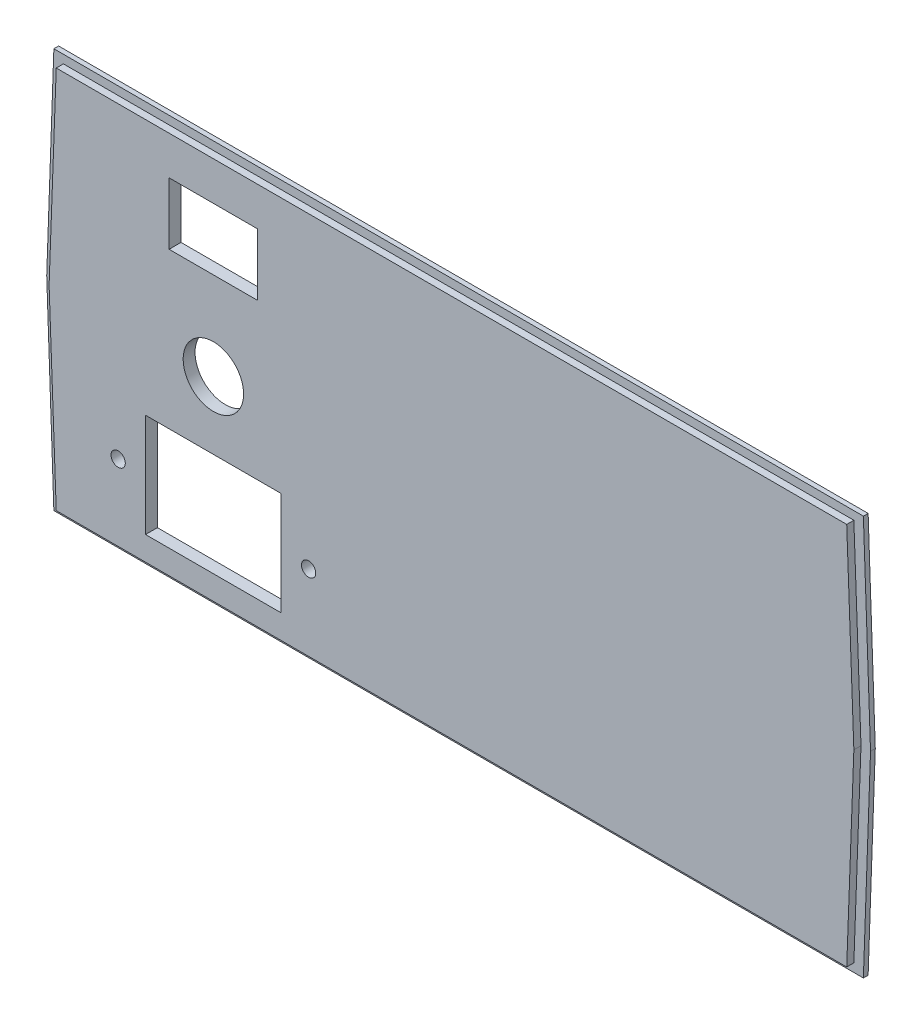
SolidWorks part; units mm, degrees
ref_plane "Front Plane" through (0, 0, 0) normal (0, 0, 1) x (1, 0, 0)
ref_plane "Top Plane" through (0, 0, 0) normal (0, 1, 0) x (1, 0, 0)
ref_plane "Right Plane" through (0, 0, 0) normal (1, 0, 0) x (0, 0, -1)
sketch "Sketch1" plane through (0, 0, 0) normal (0, 0, 1) x (1, 0, 0)
  line L1 (-85, 42) -> (85, 42)
  line L3 (-85, -42) -> (85, -42)
  line L5 (-85, 42) -> (85, -42) construction
  line L6 (-85, -42) -> (85, 42) construction
  line L7 (-86.5, 0) -> (-85, -42)
  line L8 (-85, 42) -> (-86.5, 0)
  line L9 (85, -42) -> (86.5, 0)
  line L10 (85, 42) -> (86.5, 0)
  point P0 (0, 0)
  dimension "D1" = 170
  dimension "D2" = 84
  dimension "D3" = 173
extrude "Boss-Extrude1" add sketch "Sketch1" along normal blind 1
sketch "Sketch2" plane through (0, 0, 1) normal (0, 0, 1) x (1, 0, 0)
  line L0 (-84.5, 0) -> (84.5, 0) construction
  line L1 (-83, 40.25) -> (83, 40.25)
  line L3 (-83, -40.25) -> (83, -40.25)
  line L5 (-83, 40.25) -> (83, -40.25) construction
  line L6 (-83, -40.25) -> (83, 40.25) construction
  line L7 (-83, -40.25) -> (-84.5, 0)
  line L8 (-84.5, 0) -> (-83, 40.25)
  line L9 (83, -40.25) -> (84.5, 0)
  line L10 (84.5, 0) -> (83, 40.25)
  point P0 (0, 0)
  dimension "D1" = 166
  dimension "D2" = 80.5
  dimension "D3" = 169
extrude "Boss-Extrude2" add sketch "Sketch2" along normal blind 1.5
sketch "Sketch3" plane through (0, 0, 0) normal (0, 0, -1) x (-1, 0, 0)
  line L1 (50, -24.3728) -> (50, 42) construction
  line L2 (35.75, -13.5228) -> (64.25, -13.5228)
  line L3 (35.75, -13.5228) -> (35.75, -35.2228)
  line L4 (35.75, -35.2228) -> (64.25, -35.2228)
  line L5 (-80, 40) -> (0, -40) construction
  line L6 (-80, -40) -> (0, 40) construction
  line L8 (64.25, -13.5228) -> (64.25, -35.2228)
  line L9 (35.75, -13.5228) -> (64.25, -35.2228) construction
  line L10 (35.75, -35.2228) -> (64.25, -13.5228) construction
  line L13 (-85, 42) -> (85, 42) construction
  line L14 (40.7, 32.1272) -> (59.3, 32.1272)
  line L15 (40.7, 32.1272) -> (40.7, 19.1272)
  line L16 (40.7, 19.1272) -> (59.3, 19.1272)
  line L17 (59.3, 32.1272) -> (59.3, 19.1272)
  line L18 (40.7, 32.1272) -> (59.3, 19.1272) construction
  line L19 (40.7, 19.1272) -> (59.3, 32.1272) construction
  circle A6 centre (30, -24.3728) radius 1.5
  circle A7 centre (70, -24.3728) radius 1.5
  circle A8 centre (50, 0.6272) radius 6.35
  point P26 (50, -24.3728)
  point P40 (50, 25.6272)
  dimension "D11" = 35
  dimension "D13" = 3
  dimension "D15" = 12.7
  dimension "D2" = 80
  dimension "D3" = 25
  dimension "D10" = 20
  dimension "D12" = 28.5
  dimension "D14" = 21.7
  dimension "D16" = 25
  dimension "D17" = 13
  dimension "D18" = 18.6
extrude "Cut-Extrude1" cut sketch "Sketch3" against normal up to next
